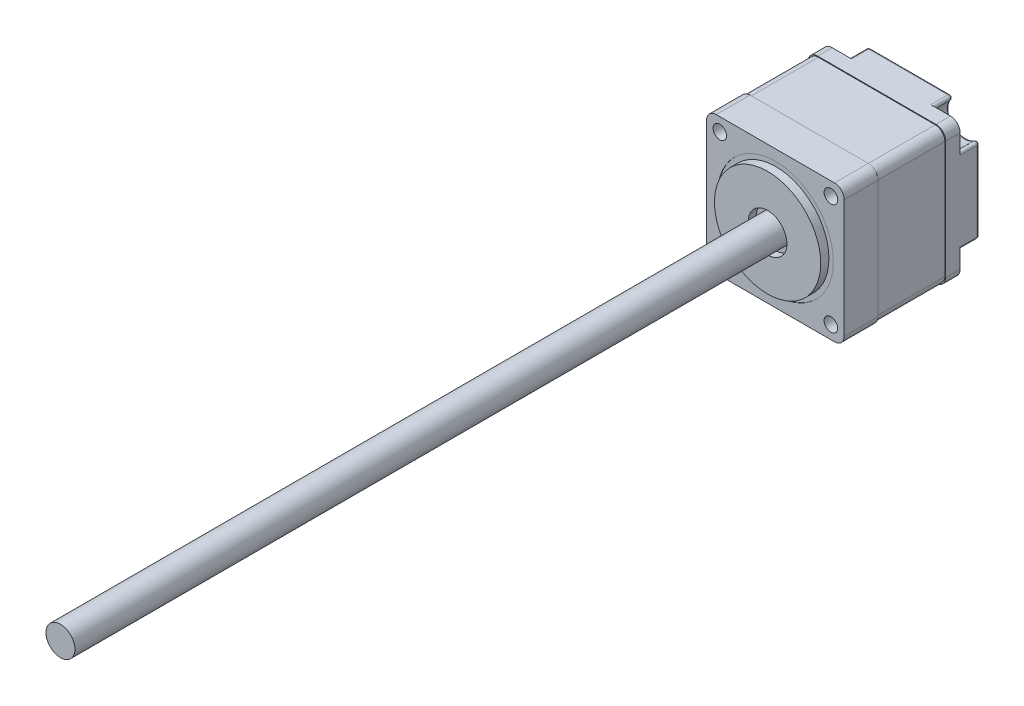
SolidWorks part; units mm, degrees
ref_plane "Front Plane" through (0, 0, 0) normal (0, 0, 1) x (1, 0, 0)
ref_plane "Top Plane" through (0, 0, 0) normal (0, 1, 0) x (1, 0, 0)
ref_plane "Right Plane" through (0, 0, 0) normal (1, 0, 0) x (0, 0, -1)
sketch "Sketch1" plane through (0, 0, 0) normal (0, 0, 1) x (1, 0, 0)
  line L1 (-14.25, 14.25) -> (14.25, 14.25)
  line L2 (-14.25, 14.25) -> (-14.25, -14.25)
  line L3 (-14.25, -14.25) -> (14.25, -14.25)
  line L4 (14.25, 14.25) -> (14.25, -14.25)
  line L5 (-14.25, 14.25) -> (14.25, -14.25) construction
  line L6 (-14.25, -14.25) -> (14.25, 14.25) construction
  point P0 (0, 0)
  dimension "D1" = 28.5
extrude "Boss-Extrude1" add sketch "Sketch1" along normal blind 7
fillet "Fillet1" radius 2 4 edges at (14.25, -14.25, 3.5) (-14.25, -14.25, 3.5) (14.25, 14.25, 3.5) (-14.25, 14.25, 3.5)
sketch "Sketch2" plane through (0, 0, 7) normal (0, 0, 1) x (1, 0, 0)
  circle A0 centre (0, 0) radius 11
  dimension "D1" = 22
extrude "Boss-Extrude2" add sketch "Sketch2" along normal blind 1.6
sketch "Sketch3" plane through (0, 0, 8.6) normal (0, 0, 1) x (1, 0, 0)
  circle A0 centre (0, 0) radius 4
  dimension "D1" = 8
extrude "Cut-Extrude1" cut sketch "Sketch3" against normal blind 1.6
sketch "Sketch4" plane through (0, 0, 7) normal (0, 0, 1) x (1, 0, 0)
  circle A0 centre (0, 0) radius 2.5
  dimension "D1" = 5
extrude "Boss-Extrude3" [suppressed] add sketch "Sketch4" along normal blind 20
sketch "Sketch5" [suppressed] plane through (0, 0, 27) normal (0, 0, 1) x (1, 0, 0)
  line L1 (-2.2, 2) -> (2.2, 2)
  line L2 (-2.2, 2) -> (-2.2, 3)
  line L3 (-2.2, 3) -> (2.2, 3)
  line L4 (2.2, 2) -> (2.2, 3)
  circle A0 centre (0, 0) radius 2.5 construction
  dimension "D1" = 2
  dimension "D2" = 1
  dimension "D3" = 2.2
  dimension "D4" = 4.4
extrude "Cut-Extrude2" [suppressed] cut sketch "Sketch5" against normal blind 20
sketch "Sketch6" plane through (0, 0, 0) normal (0, 0, -1) x (-1, 0, 0)
  line L1 (-14.1, 14.1) -> (14.1, 14.1)
  line L2 (-14.1, 14.1) -> (-14.1, -14.1)
  line L3 (-14.1, -14.1) -> (14.1, -14.1)
  line L4 (14.1, 14.1) -> (14.1, -14.1)
  line L5 (-14.1, 14.1) -> (14.1, -14.1) construction
  line L6 (-14.1, -14.1) -> (14.1, 14.1) construction
  point P0 (0, 0)
  dimension "D1" = 28.2
extrude "Boss-Extrude4" add sketch "Sketch6" along normal blind 14
fillet "Fillet2" radius 2 4 edges at (-14.1, -14.1, -7) (14.1, -14.1, -7) (-14.1, 14.1, -7) (14.1, 14.1, -7)
sketch "Sketch7" plane through (0, 0, -14) normal (0, 0, -1) x (-1, 0, 0)
  line L1 (-14.25, 14.25) -> (14.25, 14.25)
  line L2 (-14.25, 14.25) -> (-14.25, -14.25)
  line L3 (-14.25, -14.25) -> (14.25, -14.25)
  line L4 (14.25, 14.25) -> (14.25, -14.25)
  line L5 (-14.25, 14.25) -> (14.25, -14.25) construction
  line L6 (-14.25, -14.25) -> (14.25, 14.25) construction
  point P0 (0, 0)
  dimension "D1" = 28.5
extrude "Boss-Extrude5" add sketch "Sketch7" along normal blind 7
fillet "Fillet3" radius 2 4 edges at (-14.25, -14.25, -17.5) (14.25, -14.25, -17.5) (-14.25, 14.25, -17.5) (14.25, 14.25, -17.5)
sketch "Sketch9" plane through (0, 0, 7) normal (0, 0, 1) x (1, 0, 0)
  circle A0 centre (-11.5, 11.5) radius 1.4
  circle A1 centre (11.5, 11.5) radius 1.4
  circle A2 centre (11.5, -11.5) radius 1.4
  circle A3 centre (-11.5, -11.5) radius 1.4
  dimension "D1" = 2.8
  dimension "D2" = 23
  dimension "D3" = 23
  dimension "D4" = 23
  dimension "D5" = 23
  dimension "D6" = 11.5
  dimension "D7" = 11.5
  dimension "D8" = 11.5
  dimension "D9" = 11.5
extrude "Cut-Extrude3" cut sketch "Sketch9" against normal blind 42.7
sketch "Sketch10" plane through (0, 0, -21) normal (0, 0, -1) x (-1, 0, 0)
  circle A0 centre (-11.5, 11.5) radius 3.5
  circle A1 centre (11.5, 11.5) radius 3.5
  circle A2 centre (11.5, -11.5) radius 3.5
  circle A3 centre (-11.5, -11.5) radius 3.5
  dimension "D1" = 7
extrude "Cut-Extrude4" cut sketch "Sketch10" against normal blind 4
fillet "Fillet4" radius 0.5 8 edges at (-14.25, 9.3349, -19) (-9.3349, 14.25, -19) (-14.25, -9.3349, -19) (-9.3349, -14.25, -19) (9.3349, -14.25, -19) (14.25, -9.3349, -19) (9.3349, 14.25, -19) (14.25, 9.3349, -19)
fillet "Fillet5" radius 0.5 16 edges at (-13.9839, -8.6348, -21) (-9.0251, -9.0251, -21) (-8.6348, -13.9839, -21) (0, -14.25, -21) (8.6348, -13.9839, -21) (9.0251, -9.0251, -21) (13.9839, -8.6348, -21) (14.25, 0, -21) (13.9839, 8.6348, -21) (9.0251, 9.0251, -21) (8.6348, 13.9839, -21) (0, 14.25, -21) (-8.6348, 13.9839, -21) (-9.0251, 9.0251, -21) (-13.9839, 8.6348, -21) (-14.25, 0, -21)
sketch "Sketch11" plane through (0, 0, 7) normal (0, 0, 1) x (1, 0, 0)
  circle A0 centre (0, 0) radius 11
  circle A1 centre (0, 0) radius 12
  dimension "D1" = 1
extrude "Cut-Extrude5" cut sketch "Sketch11" against normal blind 0.1
sketch "Sketch12" plane through (0, 0, -21) normal (0, 0, -1) x (-1, 0, 0)
  circle A0 centre (0, 0) radius 4
  dimension "D1" = 8
extrude "Cut-Extrude6" cut sketch "Sketch12" against normal blind 2.5
sketch "Sketch13" plane through (0, 0, -18.5) normal (0, 0, -1) x (-1, 0, 0)
  circle A0 centre (0, 0) radius 2.5
  dimension "D1" = 5
extrude "Boss-Extrude7" add sketch "Sketch13" along normal blind 0.5
fillet "Fillet6" radius 0.2 1 edges at (-2.5, 0, -19)
sketch "Эскиз1" plane through (0, 0, 7) normal (0, 0, 1) x (1, 0, 0)
  circle A0 centre (0, 0) radius 3
  dimension "D1" = 6
extrude "Shaft" add sketch "Эскиз1" along normal blind 148
